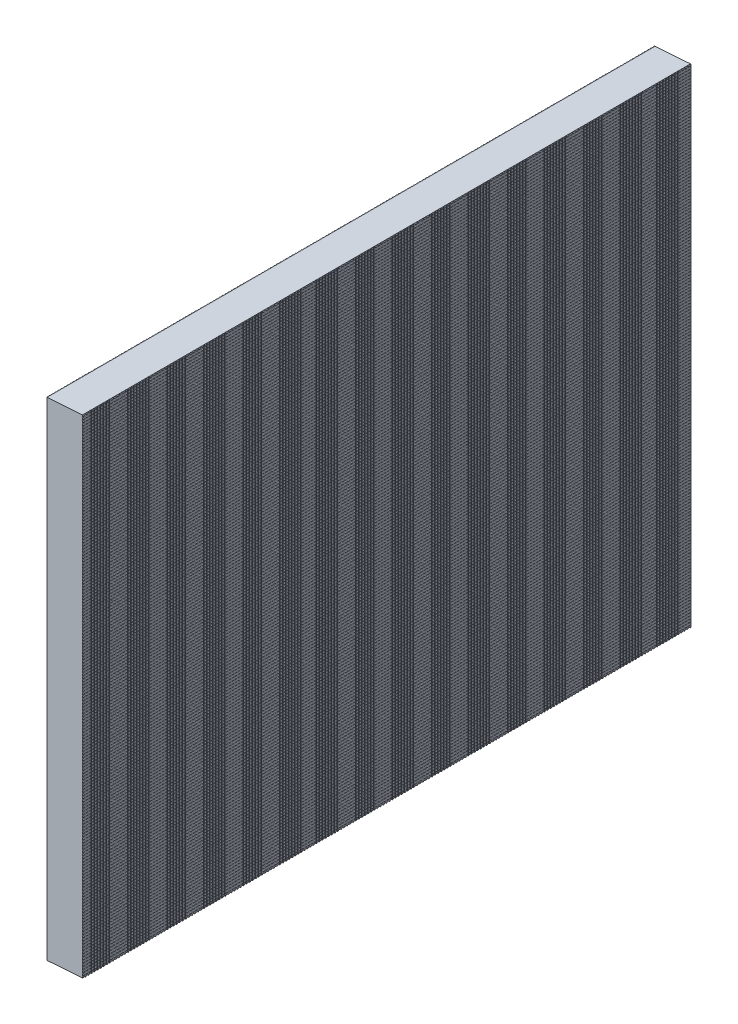
SolidWorks part; units mm, degrees
ref_plane "Front Plane" through (0, 0, 0) normal (0, 0, 1) x (1, 0, 0)
ref_plane "Top Plane" through (0, 0, 0) normal (0, 1, 0) x (1, 0, 0)
ref_plane "Right Plane" through (0, 0, 0) normal (1, 0, 0) x (0, 0, -1)
sketch "Sketch1" plane through (0, 0, 0) normal (0, 0, 1) x (1, 0, 0)
  line L0 (0, 0) -> (0, 320.8)
  line L1 (0, 320.8) -> (-23.2, 319.1777)
  line L2 (-23.2, 319.1777) -> (-23.2, -1.6223)
  line L3 (-23.2, -1.6223) -> (0, 0)
  dimension "D1" = 86
  dimension "D2" = 23.2
  dimension "D3" = 320.8
extrude "Boss-Extrude1" add sketch "Sketch1" along normal blind 400
shell "Shell1" thickness 1 removed face at (0, 160.4, 200)
sketch "Sketch2" plane through (0, 0, 0) normal (1, 0, 0) x (0, 0, -1)
  line L0 (-400, 0) -> (-400, 320.8) construction
  line L1 (-400, 320.8) -> (0, 320.8) construction
  line L2 (0, 0) -> (0, 320.8) construction
  line L3 (-400, 0) -> (0, 0) construction
  line L4 (-400, 0) -> (-400, 320.8)
  line L5 (-400, 320.8) -> (0, 320.8)
  line L6 (0, 0) -> (0, 320.8)
  line L7 (-400, 0) -> (0, 0)
extrude "Boss-Extrude2" add sketch "Sketch2" against normal blind 0.6
sketch "Sketch3" plane through (0, 0, 0) normal (0, 0, -1) x (-1, 0, 0)
  line L0 (0.6, 320.758) -> (0, 320.8)
  line L1 (0, 320.8) -> (0.6, 320.8)
  line L2 (0.6, 320.8) -> (0.6, 320.758)
extrude "Cut-Extrude1" cut sketch "Sketch3" against normal through all
sketch "Sketch4" plane through (0, 0, 0) normal (0, 0, -1) x (-1, 0, 0)
  line L0 (23.2, 319.1777) -> (23.2, 318.5777)
  line L1 (23.2, 319.1777) -> (23.2, -1.6223) construction
  line L2 (0, 319.7777) -> (0, 319.1777)
  line L3 (0, 0) -> (0, 320.8) construction
  dimension "D1" = 0.6
extrude "Extrude-Thin1" add sketch "Sketch4" against normal up to surface (400 mm away) separate body thin up to face at (-11.6, 159.5888, 400) thin type two direction wall 0.2 second wall 0.2
pattern_linear "LPattern1" count 178 spacing 1.8 along (0, -1, 0) of "Extrude-Thin1"
sketch "Sketch5" plane through (0, 319.1777, 0) normal (0, 1, 0) x (1, 0, 0)
  line L1 (-23.4, 0) -> (-23.6, 0)
  line L2 (-23.4, 0) -> (-23.4, -0.6)
  line L3 (-23.4, -0.6) -> (-23.6, -0.6)
  line L4 (-23.6, 0) -> (-23.6, -0.6)
  dimension "D1" = 0.2
  dimension "D2" = 0.6
extrude "Boss-Extrude3" add sketch "Sketch5" against normal up to vertex (320.8 mm away) separate body up to point (-23.2, -1.6223, 0)
sketch "Sketch6" plane through (0, 319.7777, 0) normal (0, 1, 0) x (1, 0, 0)
  line L1 (0.2, 0) -> (0.4, 0)
  line L2 (0.2, 0) -> (0.2, -0.6)
  line L3 (0.2, -0.6) -> (0.4, -0.6)
  line L4 (0.4, 0) -> (0.4, -0.6)
  dimension "D1" = 0.6
  dimension "D2" = 0.2
extrude "Boss-Extrude4" add sketch "Sketch6" along normal up to vertex (1.0223 mm away) and the other way up to vertex (319.7777 mm away) separate body up to point (0, 320.8, 0) other way up to point (0, 0, 0)
pattern_linear "LPattern2" count 200 spacing 2 along (0, 0, 1) of "Boss-Extrude4", "Boss-Extrude3"
sketch "Sketch7" plane through (-23.2, 0, 0) normal (-1, 0, 0) x (0, 0, 1)
  circle A0 centre (61.4, 18.3963) radius 5.295 construction
  circle A1 centre (341.4, 18.3963) radius 5.295 construction
  circle A2 centre (341.4, 298.3963) radius 5.295 construction
  circle A3 centre (61.4, 298.3963) radius 5.295 construction
  circle A4 centre (61.4, 18.3963) radius 5.295 construction
  circle A5 centre (341.4, 18.3963) radius 5.295 construction
  circle A6 centre (341.4, 298.3963) radius 5.295 construction
  circle A7 centre (61.4, 298.3963) radius 5.295 construction
  circle A8 centre (61.4, 298.3963) radius 3.15
  circle A9 centre (61.4, 298.3963) radius 7.795
  circle A10 centre (341.4, 298.3963) radius 3.15
  circle A11 centre (341.4, 298.3963) radius 7.795
  circle A12 centre (341.4, 18.3963) radius 3.15
  circle A13 centre (341.4, 18.3963) radius 7.795
  circle A14 centre (61.4, 18.3963) radius 7.795
  circle A15 centre (61.4, 18.3963) radius 3.15
  dimension "D1" = 6.3
  dimension "D2" = 2.5
extrude "Boss-Extrude5" add sketch "Sketch7" against normal up to surface (23.2 mm away) separate body up to face at (0, 160.4, 200)
sketch "Sketch8" plane through (-23.2, 0, 0) normal (-1, 0, 0) x (0, 0, 1)
  circle A0 centre (61.4, 18.3963) radius 3.15 construction
  circle A1 centre (341.4, 18.3963) radius 3.15 construction
  circle A2 centre (341.4, 298.3963) radius 3.15 construction
  circle A3 centre (61.4, 298.3963) radius 3.15 construction
  circle A4 centre (61.4, 18.3963) radius 3.15
  circle A5 centre (341.4, 18.3963) radius 3.15
  circle A6 centre (341.4, 298.3963) radius 3.15
  circle A7 centre (61.4, 298.3963) radius 3.15
